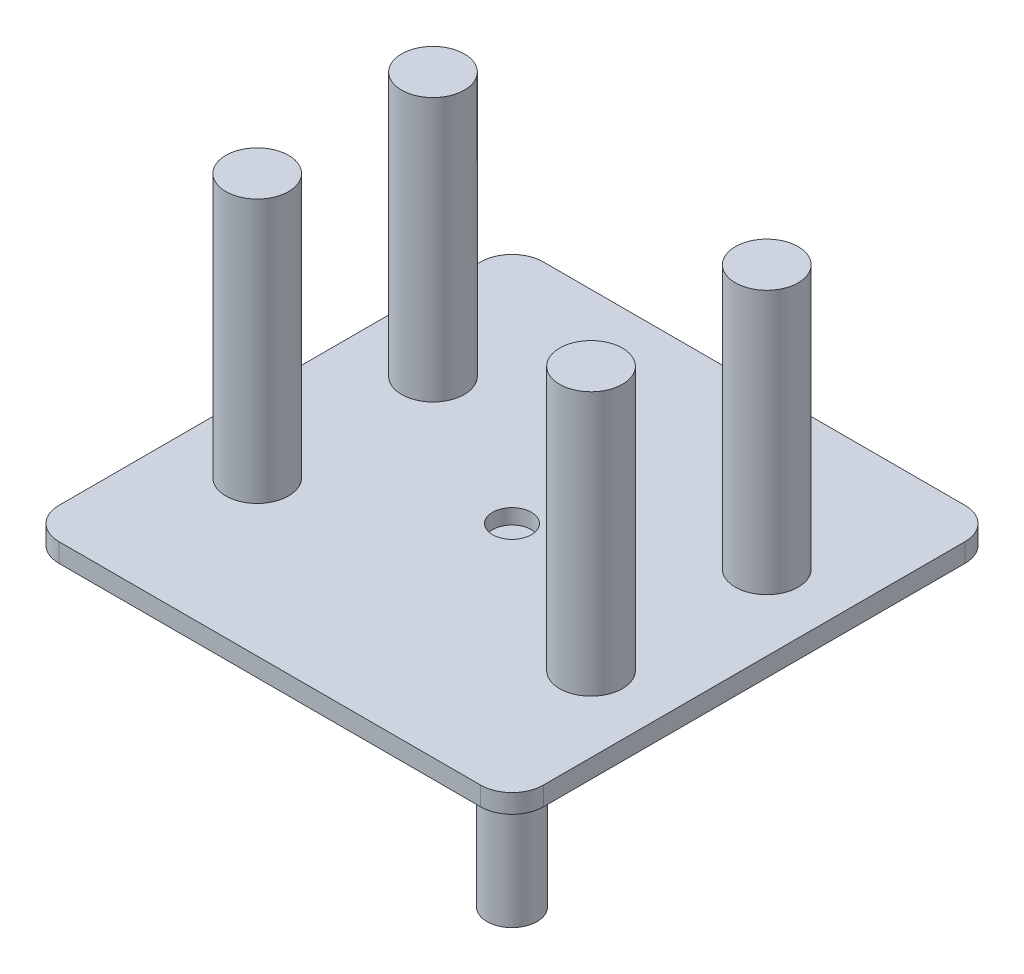
SolidWorks part; units mm, degrees
ref_plane "Płaszczyzna przednia" through (0, 0, 0) normal (0, 0, 1) x (1, 0, 0)
ref_plane "Płaszczyzna górna" through (0, 0, 0) normal (0, 1, 0) x (1, 0, 0)
ref_plane "Płaszczyzna prawa" through (0, 0, 0) normal (1, 0, 0) x (0, 0, -1)
sketch "Szkic1" plane through (0, 0, 0) normal (0, 1, 0) x (1, 0, 0)
  line L0 (0, 19.295) -> (0, -19.295) construction
  line L1 (16.795, -19.295) -> (-16.795, -19.295)
  line L2 (19.295, -16.795) -> (19.295, 16.795)
  line L3 (16.795, 19.295) -> (-16.795, 19.295)
  line L4 (-19.295, -16.795) -> (-19.295, 16.795)
  line L5 (19.295, -19.295) -> (-19.295, 19.295) construction
  line L6 (19.295, 19.295) -> (-19.295, -19.295) construction
  line L7 (-19.295, 0) -> (19.295, 0) construction
  arc A0 (-16.795, -19.295) -> (-19.295, -16.795) centre (-16.795, -16.795) cw
  arc A1 (16.795, -19.295) -> (19.295, -16.795) centre (16.795, -16.795) ccw
  arc A2 (19.295, 16.795) -> (16.795, 19.295) centre (16.795, 16.795) ccw
  arc A3 (-16.795, 19.295) -> (-19.295, 16.795) centre (-16.795, 16.795) ccw
  circle A8 centre (13.9654, -13.9654) radius 2
  circle A10 centre (-13.9654, 13.9654) radius 2
  circle A11 centre (13.295, 7) radius 2.5
  circle A12 centre (-13.295, 7) radius 2.5
  circle A13 centre (13.295, -7) radius 2.5
  circle A14 centre (-13.295, -7) radius 2.5
  point P0 (0, 0)
  point P25 (0, 0)
  point P36 (0, 0)
  dimension "D3" = 2.5
  dimension "D4" = 5
  dimension "D5" = 7
  dimension "D8" = 19.75
  dimension "D9" = 4
  dimension "D1" = 38.59
  dimension "D2" = 38.59
  dimension "D7" = 39.5
  dimension "D6" = 6
extrude "Dodanie-wyciągnięcie1" add sketch "Szkic1" along normal blind 1.5 contours L3 A3 L4 A0 L1 A1 L2 A2
extrude "Dodanie-wyciągnięcie2" add sketch "Szkic1<4>" along normal blind 22.5 contours A14 | A11 | A13 | A12 region at (-13.295, 0, 7)
sketch "Szkic1<4>" plane through (0, 0, 0) normal (0, 1, 0) x (1, 0, 0) same geometry as "Szkic1"
sketch "Szkic3" plane through (0, 1.5, 0) normal (0, -1, 0) x (1, 0, 0)
  circle A0 centre (0, 0) radius 1.55
  point P8 (0, 0)
  dimension "D1" = 3.1
extrude "Wytnij-wyciągnięcie2" cut sketch "Szkic3" along normal blind 1.2
extrude "Dodanie-wyciągnięcie3" add sketch "Szkic1<5>" against normal blind 11 contours A8 | A10
sketch "Szkic1<5>" plane through (0, 0, 0) normal (0, 1, 0) x (1, 0, 0) same geometry as "Szkic1"
sketch "Szkic2" plane through (0, -11, 0) normal (0, 1, 0) x (1, 0, 0)
  circle A0 centre (-14, 14) radius 0.85
  circle A3 centre (14, -14) radius 0.85
  circle A5 centre (14, 14) radius 0.85 [skipped]
  circle A6 centre (-14, -14) radius 0.85 [skipped]
  point P12 (0, 0)
  dimension "D1" = 14
  dimension "D3" = 1.7
  dimension "D2" = 14
  dimension "D4" = 4
extrude "Wytnij-wyciągnięcie3" cut sketch "Szkic2" along normal blind 9
